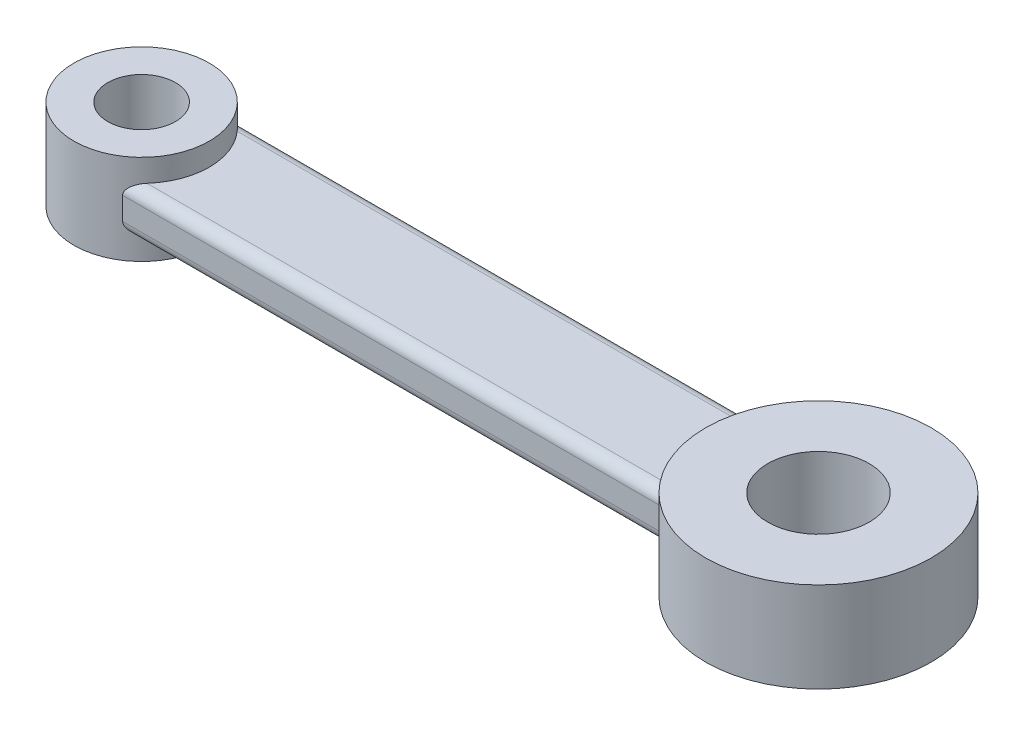
SolidWorks part; units mm, degrees
ref_plane "Front Plane" through (0, 0, 0) normal (0, 0, 1) x (1, 0, 0)
ref_plane "Top Plane" through (0, 0, 0) normal (0, 1, 0) x (1, 0, 0)
ref_plane "Right Plane" through (0, 0, 0) normal (1, 0, 0) x (0, 0, -1)
sketch "Sketch1" plane through (0, 0, 0) normal (0, 1, 0) x (1, 0, 0)
  line L1 (-15, -2.5) -> (15, -2.5)
  line L2 (-15, -2.5) -> (-15, 2.5)
  line L3 (-15, 2.5) -> (15, 2.5)
  line L4 (15, -2.5) -> (15, 2.5)
  line L5 (-15, -2.5) -> (15, 2.5) construction
  line L6 (-15, 2.5) -> (15, -2.5) construction
  point P0 (0, 0)
  dimension "D1" = 30
  dimension "D2" = 5
extrude "Boss-Extrude2" add sketch "Sketch1" along normal mid plane 2
sketch "Sketch2" plane through (0, 1, 0) normal (0, 1, 0) x (1, 0, 0)
  line L0 (-15, 2.5) -> (-15, -2.5) construction
  line L1 (15, -2.5) -> (15, 2.5) construction
  circle A0 centre (-15, 0) radius 3
  circle A1 centre (15, 0) radius 5
  dimension "D1" = 6
  dimension "D2" = 10
extrude "Boss-Extrude3" add sketch "Sketch2" along normal blind 1 and the other way blind 3
sketch "Sketch3" plane through (0, 2, 0) normal (0, 1, 0) x (1, 0, 0)
  circle A0 centre (-15, 0) radius 1.5
  circle A1 centre (15, 0) radius 2.25
  dimension "D1" = 3
  dimension "D2" = 4.5
extrude "Cut-Extrude1" cut sketch "Sketch3" against normal blind 41
fillet "Fillet1" radius 0.5 2 edges at (-1.3359, 1, 2.5) (-1.3359, 1, -2.5)
fillet "Fillet2" radius 0.5 2 edges at (-1.3359, -1, -2.5) (-1.3359, -1, 2.5)
